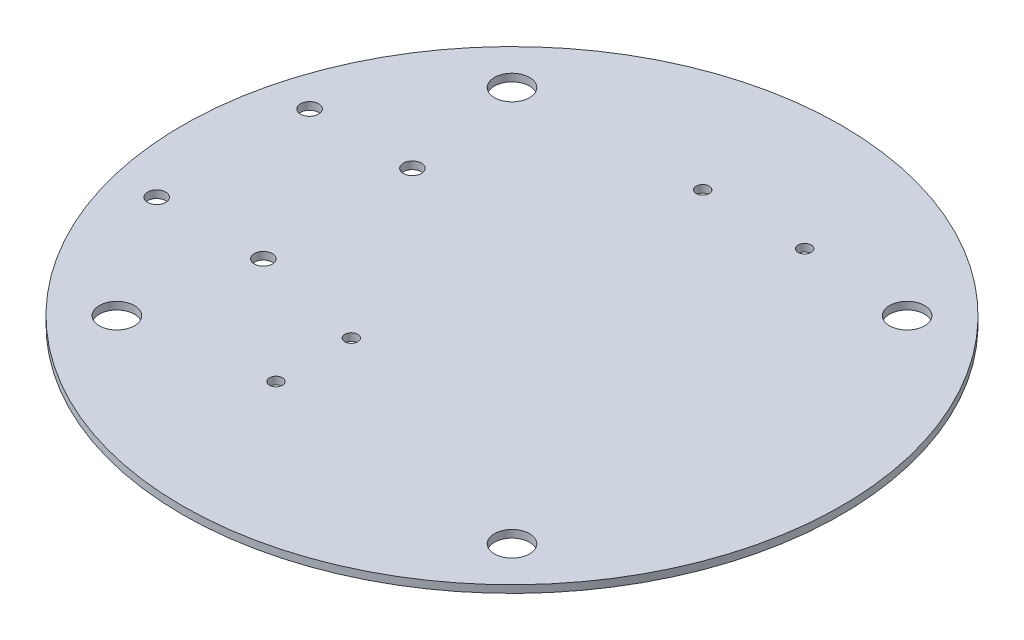
SolidWorks part; units mm, degrees
ref_plane "Front Plane" through (0, 0, 0) normal (0, 0, 1) x (1, 0, 0)
ref_plane "Top Plane" through (0, 0, 0) normal (0, 1, 0) x (1, 0, 0)
ref_plane "Right Plane" through (0, 0, 0) normal (1, 0, 0) x (0, 0, -1)
sketch "Sketch1" plane through (0, 0, 0) normal (0, 1, 0) x (1, 0, 0)
  circle A0 centre (0, 0) radius 65.7
  dimension "PCBdiam" = 131.4
extrude "Boss-Extrude1" add sketch "Sketch1" along normal blind 1.5
hole_wizard "M6 Clearance Hole1" positions "Sketch2" profile "Sketch4" hole size "M6" standard "ANSI Metric" end condition through all
sketch "Sketch2" plane through (0, 1.5, 0) normal (0, 1, 0) x (1, 0, 0)
  line L0 (0, 0) -> (-28.5457, 28.5457) construction
  line L1 (-39.3858, -39.3858) -> (0, 0) construction
  line L3 (0, 0) -> (-73.422, 0) construction
  circle A0 centre (0, 0) radius 65.7 construction
  ellipse E2 centre (-116.4291, -176.9435) end of major axis (-117.7556, -176.0714) minor radius 1.3748
  ellipse E3 centre (-116.4291, -176.9435) end of major axis (-115.1026, -177.8157) minor radius 1.3748
  point P7 (-39.3858, -39.3858)
  dimension "D1" = 0
  dimension "holeRadius" = 55.7
  dimension "D2" = 45
sketch "Sketch4" plane through (-39.3858, 1.5, 39.3858) normal (1, 0, 0) x (0, 0, 1)
  line L0 (0, 0) -> (0, 1.5)
  line L1 (0, 1.5) -> (3.5, 1.5)
  line L2 (3.5, 1.5) -> (3.5, 0)
  line L5 (3.5, 0) -> (0, 0)
  line L11 (0, -6.35) -> (0, 107.95) construction
  dimension "Thru Hole Dia." = 7
  dimension "Thru Hole Depth" = 1.5
pattern_circular "CirPattern1" count 4 over 360 about axis through (0, 1.5, 0) along (0, -1, 0) of "M6 Clearance Hole1"
sketch "Teensy Outline" plane through (0, 1.5, 0) normal (0, 1, 0) x (1, 0, 0)
  line L1 (-29.654, 50.7) -> (-12, 50.7)
  line L2 (-29.654, 50.7) -> (-29.654, -7.72)
  line L3 (-29.654, -7.72) -> (-12, -7.72)
  line L4 (-12, 50.7) -> (-12, -7.72)
  circle A1 centre (0, 0) radius 65.7 construction
  dimension "D1" = 17.654
  dimension "D2" = 58.42
  dimension "D3" = 12
  dimension "D4" = 15
sketch "BMP390 Outline" plane through (0, 1.5, 0) normal (0, 1, 0) x (1, 0, 0)
  line L0 (17.61, 54.7) -> (-5.25, 54.7) construction
  line L2 (20.15, 56.04) -> (-5.25, 56.04)
  line L3 (-5.25, 56.04) -> (-5.25, 38.26)
  line L4 (20.15, 38.26) -> (-5.25, 38.26)
  line L6 (20.15, 56.04) -> (20.15, 38.26)
  line L7 (17.61, 54.7) -> (17.61, 38.26) construction
  line L8 (-29.654, 50.7) -> (-12, 50.7) construction
  line L9 (-12, 50.7) -> (-12, -7.72) construction
  dimension "D1" = 17.78
  dimension "D2" = 25.4
  dimension "D3" = 1.34
  dimension "D4" = 4
  dimension "D5" = 6.75
  dimension "D6" = 5.08
sketch "NEO-6M Outline" plane through (0, 1.5, 0) normal (0, 1, 0) x (1, 0, 0)
  line L0 (-50.84, 17.78) -> (-50.84, 15.24) construction
  line L1 (-58.34, 17.78) -> (-32, 17.78)
  line L2 (-58.34, 17.78) -> (-58.34, -17.78)
  line L3 (-58.34, -17.78) -> (-32, -17.78)
  line L4 (-32, 17.78) -> (-32, -17.78)
  line L5 (-50.84, 15.24) -> (-39.5, 15.24) construction
  line L6 (-39.5, 15.24) -> (-39.5, 17.78) construction
  point P4 (-32, 0)
  point P9 (-45.17, 15.24)
  point P11 (-45.17, 17.78)
  dimension "D1" = 26.34
  dimension "D2" = 35.56
  dimension "D3" = 32
  dimension "D4" = 7.5
  dimension "D5" = 2.54
sketch "Xbee outline" plane through (0, 1.5, 0) normal (0, 1, 0) x (1, 0, 0)
  line L0 (9, 6.5) -> (26, 6.5) construction
  line L1 (26, 1.875) -> (26, 11.125)
  line L2 (26, 11.125) -> (19.5, 18.75)
  line L3 (19.5, 18.75) -> (-7, 18.75)
  line L4 (-7, 18.75) -> (-7, -5.75)
  line L5 (19.5, -5.75) -> (-7, -5.75)
  line L6 (26, 1.875) -> (19.5, -5.75)
  line L7 (0, 0) -> (72.9219, 0) construction
  line L9 (-12, 50.7) -> (-12, -7.72) construction
  line L10 (61, 12) -> (26, 12) construction
  line L11 (61, 12) -> (61, 1) construction
  line L12 (61, 1) -> (26, 1) construction
  line L13 (26, 12) -> (26, 1) construction
  point P7 (-7, 6.5)
  point P11 (26, 6.5)
  dimension "D1" = 24.5
  dimension "D2" = 33
  dimension "D3" = 26.5
  dimension "D4" = 9.25
  dimension "D5" = 16
  dimension "D6" = 35
  dimension "D7" = 11
  dimension "D8" = 6.5
  dimension "D9" = 5
sketch "Accel, gyro outline" plane through (0, 1.5, 0) normal (0, 1, 0) x (1, 0, 0)
  line L0 (47.32, 31.44) -> (27, 31.44) construction
  line L1 (52.4, 32.78) -> (27, 32.78)
  line L2 (27, 32.78) -> (27, 15)
  line L3 (52.4, 15) -> (27, 15)
  line L4 (52.4, 32.78) -> (52.4, 15)
  line L5 (47.32, 31.44) -> (47.32, 16.34) construction
  line L6 (27, 23.89) -> (52.4, 23.89) construction
  line L7 (47.32, 16.34) -> (27, 16.34) construction
  dimension "D1" = 17.78
  dimension "D2" = 25.4
  dimension "D3" = 1.34
  dimension "D4" = 5.08
  dimension "D5" = 15
  dimension "D6" = 27
sketch "Sketch17" plane through (0, 1.5, 0) normal (0, 1, 0) x (1, 0, 0)
  line L0 (-29.654, -23.3858) -> (-36.154, -23.3858) construction
  line L1 (-29.654, -17.3858) -> (-9.654, -17.3858)
  line L2 (-29.654, -17.3858) -> (-29.654, -37.3858)
  line L3 (-29.654, -37.3858) -> (-9.654, -37.3858)
  line L4 (-9.654, -17.3858) -> (-9.654, -37.3858)
  line L5 (-36.154, -23.3858) -> (-36.154, -31.3858) construction
  line L6 (-36.154, -31.3858) -> (-29.654, -31.3858) construction
  line L7 (-29.654, 50.7) -> (-29.654, -7.72) construction
  circle A0 centre (-39.3858, -39.3858) radius 3.5 construction
  point P8 (-36.154, -27.3858)
  point P9 (-29.654, -27.3858)
  dimension "D1" = 20
  dimension "D2" = 20
  dimension "D3" = 6.5
  dimension "D4" = 8
  dimension "D5" = 0
  dimension "D6" = 2
hole_wizard "M2 Clearance Hole1" positions "Sketch20" profile "Sketch19" hole size "M2" standard "ANSI Metric" end condition through all
sketch "Sketch20" plane through (0, 1.5, 0) normal (0, 1, 0) x (1, 0, 0)
  circle A0 centre (-2.71, 40.73) radius 1.2493 construction
  circle A1 centre (17.61, 40.73) radius 1.2493 construction
  circle A2 centre (-12.154, -19.8858) radius 1.25 construction
  circle A3 centre (-12.154, -19.8858) radius 1.25 construction
  circle A4 centre (-12.154, -34.8858) radius 1.25 construction
  circle A5 centre (-12.154, -34.8858) radius 1.25 construction
  point P1 (-2.71, 40.73)
  point P7 (17.61, 40.73)
  point P13 (-12.154, -19.8858)
  point P16 (-12.154, -34.8858)
sketch "Sketch19" plane through (-2.71, 1.5, -40.73) normal (1, 0, 0) x (0, 0, 1)
  line L0 (0, 0) -> (0, 1.5)
  line L1 (0, 1.5) -> (1.3, 1.5)
  line L2 (1.3, 1.5) -> (1.3, 0)
  line L5 (1.3, 0) -> (0, 0)
  line L11 (0, -6.35) -> (0, 107.95) construction
  dimension "Thru Hole Dia." = 2.6
  dimension "Thru Hole Depth" = 1.5
hole_wizard "M3 Clearance Hole2" positions "Sketch21" profile "Sketch22" hole size "M3" standard "ANSI Metric" end condition through all
sketch "Sketch21" plane through (0, 1.5, 0) normal (0, 1, 0) x (1, 0, 0)
  point P0 (-55.8645, 15.5117)
  point P3 (-55.8645, -14.9683)
  point P6 (-34.6045, -14.9683)
  point P9 (-35.3665, 15.5117)
sketch "Sketch22" plane through (-55.8645, 1.5, -15.5117) normal (1, 0, 0) x (0, 0, 1)
  line L0 (0, 0) -> (0, 1.5)
  line L1 (0, 1.5) -> (1.8, 1.5)
  line L2 (1.8, 1.5) -> (1.8, 0)
  line L5 (1.8, 0) -> (0, 0)
  line L11 (0, -6.35) -> (0, 107.95) construction
  dimension "Thru Hole Dia." = 3.6
  dimension "Thru Hole Depth" = 1.5
